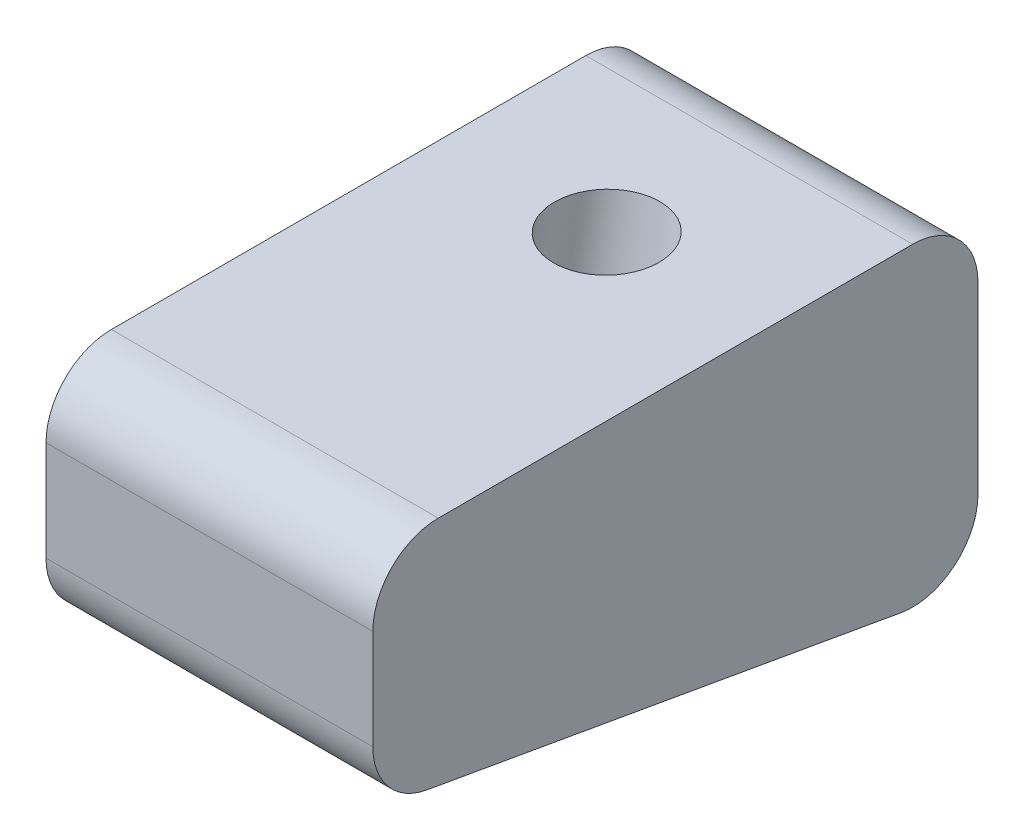
SolidWorks part; units mm, degrees
ref_plane "Front Plane" through (0, 0, 0) normal (0, 0, 1) x (1, 0, 0)
ref_plane "Top Plane" through (0, 0, 0) normal (0, 1, 0) x (1, 0, 0)
ref_plane "Right Plane" through (0, 0, 0) normal (1, 0, 0) x (0, 0, -1)
sketch "Sketch1" plane through (0, 0, 0) normal (1, 0, 0) x (0, 0, -1)
  line L0 (0, 0) -> (-46.286, 0)
  line L2 (0, -25) -> (0, 0)
  line L3 (0, -25) -> (-46.286, -16.8385)
  line L4 (-46.286, -16.8385) -> (-46.286, 0)
  dimension "D1" = 47
  dimension "D2" = 25
  dimension "D3" = 80
extrude "Boss-Extrude1" add sketch "Sketch1" along normal blind 25
sketch "Sketch2" plane through (0, -24.2462, 4.2753) normal (0, -0.9848, 0.1736) x (1, 0, 0)
  line L0 (25, -4.3412) -> (0, -4.3412) construction
  circle A0 centre (12.5, 15.6588) radius 4
  dimension "D1" = 8
  dimension "D2" = 20
extrude "Cut-Extrude1" cut sketch "Sketch2" against normal blind 25
fillet "Fillet1" radius 5 4 edges at (12.5, -16.8385, 46.286) (12.5, -25, 0) (12.5, 0, 0) (12.5, 0, 46.286)
